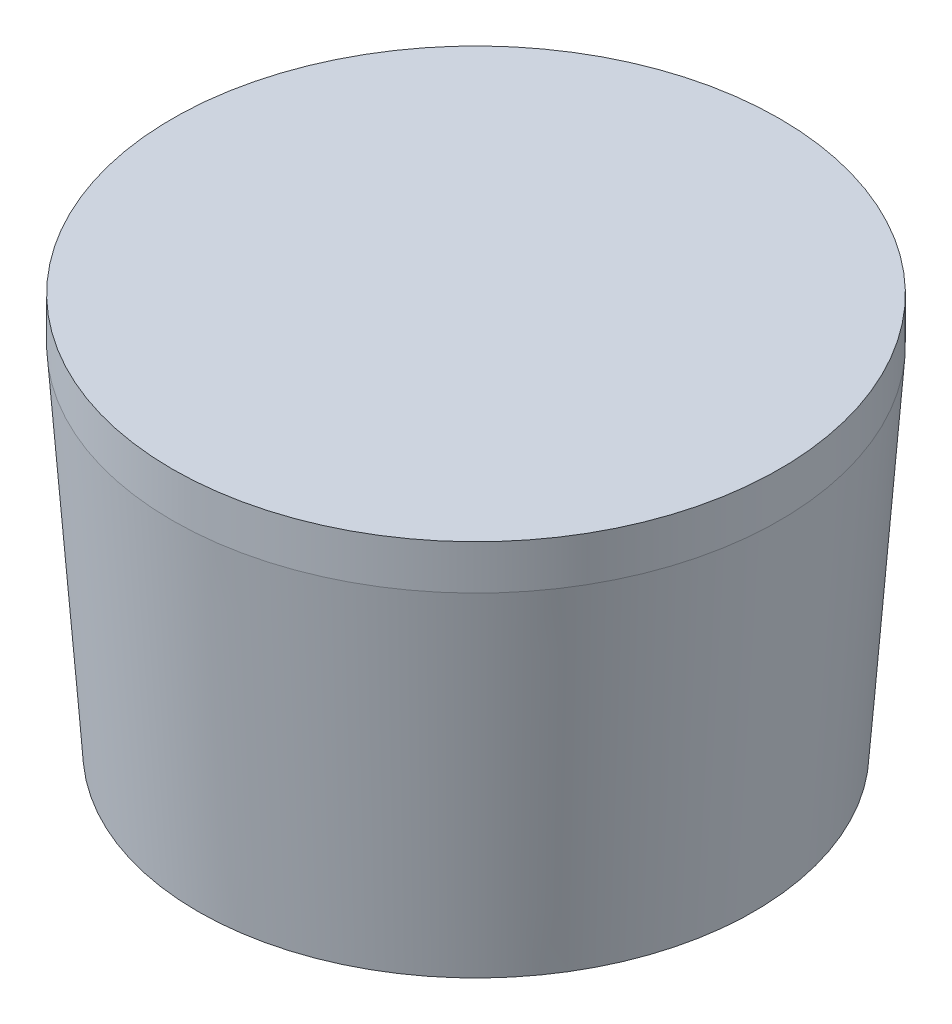
SolidWorks part; units mm, degrees
ref_plane "Front Plane" through (0, 0, 0) normal (0, 0, 1) x (1, 0, 0)
ref_plane "Top Plane" through (0, 0, 0) normal (0, 1, 0) x (1, 0, 0)
ref_plane "Right Plane" through (0, 0, 0) normal (1, 0, 0) x (0, 0, -1)
sketch "Çizim9" plane through (0, 0, 0) normal (0, 1, 0) x (1, 0, 0)
  circle A0 centre (0, 0) radius 125
ref_plane "Düzlem4" through (0, 158, 0) normal (0, 1, 0) x (1, 0, 0)
sketch "Çizim10" plane through (0, 158, 0) normal (0, 1, 0) x (1, 0, 0)
  circle A0 centre (0, 0) radius 136.5
loft "Loft2" add profiles "Çizim10", "Çizim9" connector at (135.5888, 158, -15.7457) connector at (124.1473, 0, -14.5752)
sketch "Çizim11" plane through (0, 158, 0) normal (0, 1, 0) x (1, 0, 0)
  circle A0 centre (0, 0) radius 136.5
extrude "Yükseklik-Ekstrüzyon2" add sketch "Çizim11" along normal blind 20
sketch "Çizim12" plane through (0, 0, 0) normal (0, -1, 0) x (1, 0, 0)
  circle A0 centre (0, 0) radius 79
extrude "Kes-Ekstrüzyon3" cut sketch "Çizim12" against normal blind 12.5
dome "Kubbe3" faces to dome 1 distance 5 reverse direction yes elliptical dome no face at (0, 12.5, -79) parameters "D1"=5
